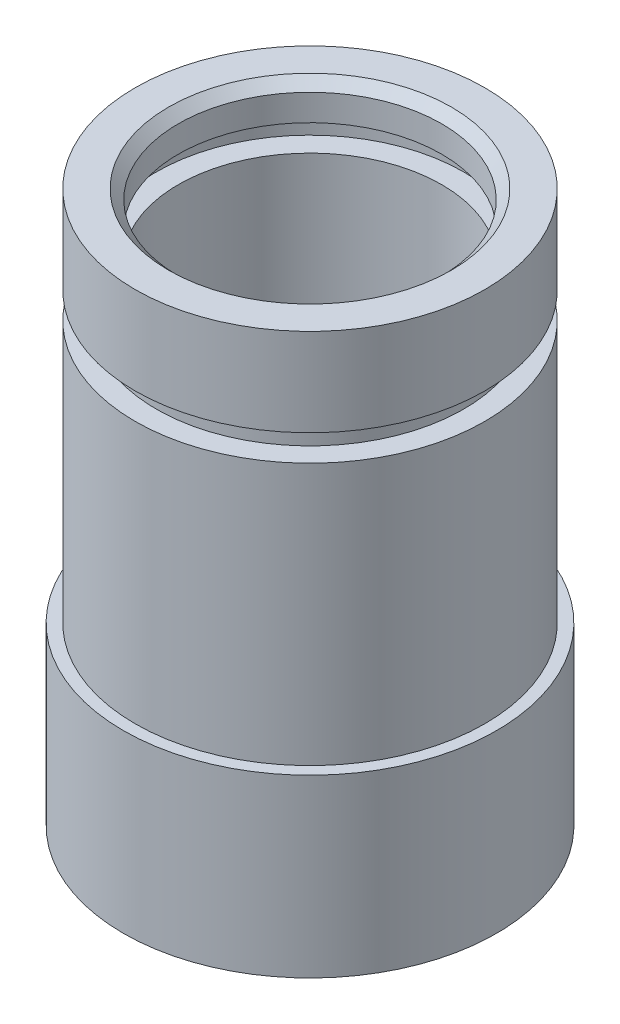
SolidWorks part; units mm, degrees
material "6061 Alloy"
ref_plane "Front Plane" through (0, 0, 0) normal (0, 0, 1) x (1, 0, 0)
ref_plane "Top Plane" through (0, 0, 0) normal (0, 1, 0) x (1, 0, 0)
ref_plane "Right Plane" through (0, 0, 0) normal (1, 0, 0) x (0, 0, -1)
sketch "Sketch1" plane through (0, 0, 0) normal (0, 0, 1) x (1, 0, 0)
  line L0 (0, 0) -> (0, 10.9165) construction
  line L1 (19.05, -70.3721) -> (19.05, -28.7161)
  line L2 (19.05, -28.7161) -> (20.447, -27.3191)
  line L3 (20.447, -27.3191) -> (25.2857, -27.3191)
  line L6 (25.2857, -27.3191) -> (25.2857, -70.3721)
  line L7 (25.2857, -70.3721) -> (19.05, -70.3721)
  line L8 (19.05, -70.3721) -> (15.875, -70.3721)
  line L9 (15.875, -70.3721) -> (25.7175, -107.1048)
  line L11 (25.7175, -107.1048) -> (26.9875, -107.1048)
  line L13 (15.875, -70.3721) -> (7.9375, -40.7489) construction
  line L14 (26.9875, -81.7048) -> (26.9875, -107.1048)
  line L15 (25.2857, -70.3721) -> (25.2857, -81.7048)
  line L16 (-26.9875, -81.7048) -> (26.9875, -81.7048) construction
  line L17 (25.2857, -81.7048) -> (26.9875, -81.7048)
  line L18 (-26.9875, -81.7048) -> (-26.9875, -107.1048)
  line L19 (-26.9875, -107.1048) -> (26.9875, -107.1048) construction
  line L20 (-22.2123, -27.3191) -> (22.2123, -27.3191) construction
  line L21 (19.05, -32.5261) -> (22.225, -32.5261)
  line L22 (25.2857, -40.0191) -> (22.225, -40.0191)
  line L23 (25.2857, -40.0191) -> (25.2857, -43.8291)
  line L24 (25.2857, -43.8291) -> (22.225, -43.8291)
  line L25 (22.225, -40.0191) -> (22.225, -43.8291)
  line L26 (19.05, -32.5261) -> (19.05, -36.3361)
  line L27 (19.05, -36.3361) -> (22.225, -36.3361)
  line L28 (22.225, -32.5261) -> (22.225, -36.3361)
  line L29 (-25.7175, -107.1048) -> (-26.9875, -107.1048)
  line L30 (-15.875, -70.3721) -> (-25.7175, -107.1048)
  line L31 (-22.225, -32.5261) -> (-22.225, -36.3361)
  line L32 (-19.05, -36.3361) -> (-22.225, -36.3361)
  line L33 (-19.05, -32.5261) -> (-19.05, -36.3361)
  line L34 (-22.225, -40.0191) -> (-22.225, -43.8291)
  line L35 (-25.2857, -43.8291) -> (-22.225, -43.8291)
  line L36 (-25.2857, -40.0191) -> (-25.2857, -43.8291)
  line L37 (-25.2857, -40.0191) -> (-22.225, -40.0191)
  line L38 (-19.05, -32.5261) -> (-22.225, -32.5261)
  line L39 (-25.2857, -81.7048) -> (-26.9875, -81.7048)
  line L40 (-25.2857, -70.3721) -> (-25.2857, -81.7048)
  line L41 (-19.05, -70.3721) -> (-15.875, -70.3721)
  line L42 (-25.2857, -70.3721) -> (-19.05, -70.3721)
  line L43 (-25.2857, -27.3191) -> (-25.2857, -70.3721)
  line L44 (-20.447, -27.3191) -> (-25.2857, -27.3191)
  line L45 (-19.05, -28.7161) -> (-20.447, -27.3191)
  line L46 (-19.05, -70.3721) -> (-19.05, -28.7161)
  point P26 (25.2857, -27.3191)
  point P37 (15.875, -70.3721)
  point P53 (-15.875, -70.3721)
  point P54 (-25.2857, -27.3191)
  dimension "D1" = 44.45
  dimension "D2" = 12.7
  dimension "D3" = 44.45
  dimension "D4" = 3.81
  dimension "D5" = 19.05
  dimension "D6" = 45
  dimension "D7" = 1.397
  dimension "D8" = 3.0607
  dimension "D9" = 3.81
revolve "Revolve1" add sketch "Sketch1" angle 360 about L0 region at (22.1785, -49.9764, 0) region at (22.9715, -84.598, 0)
